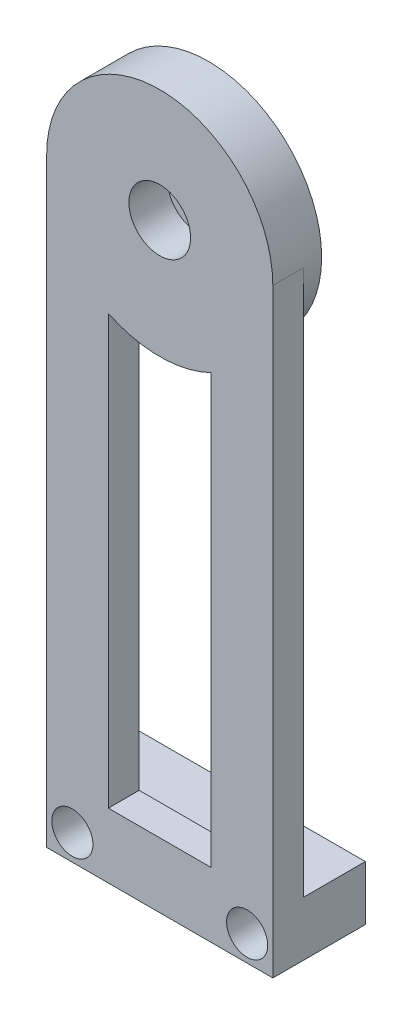
SolidWorks part; units mm, degrees
ref_plane "Front Plane" through (0, 0, 0) normal (0, 0, 1) x (1, 0, 0)
ref_plane "Top Plane" through (0, 0, 0) normal (0, 1, 0) x (1, 0, 0)
ref_plane "Right Plane" through (0, 0, 0) normal (1, 0, 0) x (0, 0, -1)
sketch "Sketch1" plane through (0, 0, 0) normal (0, 0, 1) x (1, 0, 0)
  line L0 (0, 29.175) -> (0, -29.175) construction
  line L1 (-11, 29.175) -> (-11, -29.175)
  line L2 (11, 29.175) -> (11, -29.175)
  line L3 (-11, -29.175) -> (11, -29.175)
  line L5 (-11, -29.175) -> (11, -29.175)
  line L6 (-11, -29.175) -> (-11, -23.865)
  line L7 (-11, -23.865) -> (11, -23.865)
  line L8 (11, -29.175) -> (11, -23.865)
  line L10 (-5, 18.8188) -> (-5, -22.865)
  line L11 (-5, -22.865) -> (5, -22.865)
  line L12 (5, 18.8188) -> (5, -22.865)
  circle A0 centre (0, 29.175) radius 11
  arc A2 (-5, 18.8188) -> (5, 18.8188) centre (0, 29.175) ccw
  point P8 (0, 0)
  dimension "D2" = 22
  dimension "D6" = 6
  dimension "D7" = 11.5
  dimension "D1" = 58.35
  dimension "D3" = 5.31
  dimension "D4" = 1
  dimension "D5" = 6
extrude "Boss-Extrude1" add sketch "Sketch1" along normal blind 3 contours A0 | L0 A0 L1 | A0 L0 L2 | L6 L5 L8 L7 region at (0, 18.1176, 0) region at (0, 29.175, 0)
extrude "Boss-Extrude2" add sketch "Sketch1<3>" against normal blind 1.75 contours A0 region at (0, 29.175, 0)
sketch "Sketch1<3>" plane through (0, 0, 0) normal (0, 0, 1) x (1, 0, 0) same geometry as "Sketch1"
sketch "Sketch2" plane through (0, 0, 3) normal (0, 0, 1) x (1, 0, 0)
  circle A0 centre (0, 29.175) radius 1.75
  circle A3 centre (0, 29.175) radius 3
  dimension "D1" = 3.5
  dimension "D2" = 6
extrude "Cut-Extrude1" cut sketch "Sketch2" against normal up to surface (4.75 mm away) contours A0 region at (0, 29.175, 3) up to face at (11, 29.175, -1.75)
extrude "Cut-Extrude2" cut sketch "Sketch2<3>" against normal offset from surface (3.75 mm away) 1 contours A3 A0 region at (-2.9151, 29.175, 3) up to face at (1.75, 29.175, -1.75)
sketch "Sketch2<3>" plane through (0, 0, 3) normal (0, 0, 1) x (1, 0, 0) same geometry as "Sketch2"
extrude "Boss-Extrude3" add sketch "Sketch1<6>" against normal blind 6 contours L7 L0 L5 L2 | L0 L7 L1 L3 region at (-5.5, -26.52, 0) region at (5.5, -26.52, 0)
sketch "Sketch1<6>" plane through (0, 0, 0) normal (0, 0, 1) x (1, 0, 0) same geometry as "Sketch1"
sketch "Sketch3" plane through (0, 0, 3) normal (0, 0, 1) x (1, 0, 0)
  line L1 (-8.5, -26.68) -> (8.5, -26.68) construction
  line L2 (-11, -29.175) -> (11, -29.175) construction
  circle A1 centre (-8.5, -26.68) radius 1.1
  circle A2 centre (8.5, -26.68) radius 1.1
  circle A3 centre (-8.5, -26.68) radius 2
  circle A4 centre (8.5, -26.68) radius 2
  point P5 (0, -26.68)
  dimension "D2" = 2.2
  dimension "D3" = 4
  dimension "D4" = 2.495
  dimension "D1" = 17
extrude "Cut-Extrude3" cut sketch "Sketch3" against normal up to surface (9 mm away) contours A1 | A2 region at (-8.5, -26.68, 3) up to face at (0, -26.52, -6)
extrude "Cut-Extrude4" cut sketch "Sketch3<3>" against normal offset from surface (8 mm away) 1 up to face at (-7.4, -26.68, -6)
sketch "Sketch3<3>" plane through (0, 0, 3) normal (0, 0, 1) x (1, 0, 0) same geometry as "Sketch3"
